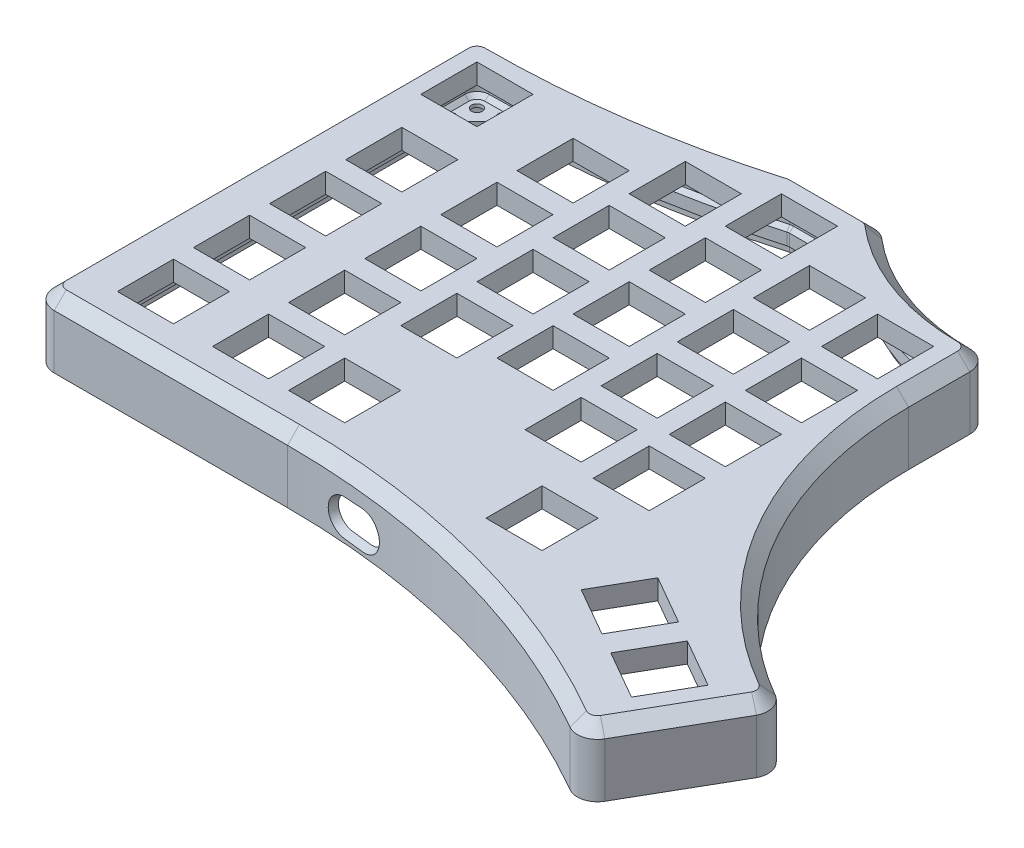
SolidWorks part; units mm, degrees
ref_plane "Front Plane" through (0, 0, 0) normal (0, 0, 1) x (1, 0, 0)
ref_plane "Top Plane" through (0, 0, 0) normal (0, 1, 0) x (1, 0, 0)
ref_plane "Right Plane" through (0, 0, 0) normal (1, 0, 0) x (0, 0, -1)
sketch "Main" plane through (0, 0, 0) normal (0, 1, 0) x (1, 0, 0)
  line L0 (6.4754, 3.5) -> (12.8, 6.5) construction
  line L1 (0, 0) -> (18, 0) construction
  line L2 (0, 0) -> (0, 18) construction
  line L3 (0, 18) -> (18, 18) construction
  line L4 (18, 0) -> (18, 18) construction
  line L5 (2, 16) -> (16, 16)
  line L6 (2, 16) -> (2, 2)
  line L7 (2, 2) -> (16, 2)
  line L8 (16, 16) -> (16, 2)
  line L18 (9, 9) -> (6.4754, 3.5) construction
  line L20 (9, 9) -> (12.8, 6.5) construction
  line L22 (25.4754, 12.5) -> (31.8, 15.5) construction
  line L23 (19, 9) -> (37, 9) construction
  line L24 (19, 9) -> (19, 27) construction
  line L25 (19, 27) -> (37, 27) construction
  line L26 (37, 9) -> (37, 27) construction
  line L27 (21, 25) -> (35, 25)
  line L28 (21, 25) -> (21, 11)
  line L29 (21, 11) -> (35, 11)
  line L30 (35, 25) -> (35, 11)
  line L31 (28, 18) -> (25.4754, 12.5) construction
  line L32 (28, 18) -> (31.8, 15.5) construction
  line L33 (44.4754, 17.5) -> (50.8, 20.5) construction
  line L34 (38, 14) -> (56, 14) construction
  line L35 (38, 14) -> (38, 32) construction
  line L36 (38, 32) -> (56, 32) construction
  line L37 (56, 14) -> (56, 32) construction
  line L38 (40, 30) -> (54, 30)
  line L39 (40, 30) -> (40, 16)
  line L40 (40, 16) -> (54, 16)
  line L41 (54, 30) -> (54, 16)
  line L42 (47, 23) -> (44.4754, 17.5) construction
  line L43 (47, 23) -> (50.8, 20.5) construction
  line L44 (63.4754, 5.5) -> (69.8, 8.5) construction
  line L45 (57, 2) -> (75, 2) construction
  line L46 (57, 2) -> (57, 20) construction
  line L47 (57, 20) -> (75, 20) construction
  line L48 (75, 2) -> (75, 20) construction
  line L49 (59, 18) -> (73, 18)
  line L50 (59, 18) -> (59, 4)
  line L51 (59, 4) -> (73, 4)
  line L52 (73, 18) -> (73, 4)
  line L53 (66, 11) -> (63.4754, 5.5) construction
  line L54 (66, 11) -> (69.8, 8.5) construction
  line L55 (82.4754, 3.5) -> (88.8, 6.5) construction
  line L56 (76, 0) -> (94, 0) construction
  line L57 (76, 0) -> (76, 18) construction
  line L58 (76, 18) -> (94, 18) construction
  line L59 (94, 0) -> (94, 18) construction
  line L60 (78, 16) -> (92, 16)
  line L61 (78, 16) -> (78, 2)
  line L62 (78, 2) -> (92, 2)
  line L63 (92, 16) -> (92, 2)
  line L64 (85, 9) -> (82.4754, 3.5) construction
  line L65 (85, 9) -> (88.8, 6.5) construction
  line L88 (2, -3) -> (16, -3)
  line L89 (2, -3) -> (2, -17)
  line L90 (2, -17) -> (16, -17)
  line L91 (16, -3) -> (16, -17)
  line L92 (21, 6) -> (35, 6)
  line L93 (21, 6) -> (21, -8)
  line L94 (21, -8) -> (35, -8)
  line L95 (35, 6) -> (35, -8)
  line L96 (40, 11) -> (54, 11)
  line L97 (40, 11) -> (40, -3)
  line L98 (40, -3) -> (54, -3)
  line L99 (54, 11) -> (54, -3)
  line L100 (59, -1) -> (73, -1)
  line L101 (59, -1) -> (59, -15)
  line L102 (59, -15) -> (73, -15)
  line L103 (73, -1) -> (73, -15)
  line L104 (78, -3) -> (92, -3)
  line L105 (78, -3) -> (78, -17)
  line L106 (78, -17) -> (92, -17)
  line L107 (92, -3) -> (92, -17)
  line L116 (6.4754, -15.5) -> (12.8, -12.5) construction
  line L117 (0, -19) -> (18, -19) construction
  line L118 (0, -19) -> (0, -1) construction
  line L119 (0, -1) -> (18, -1) construction
  line L120 (18, -19) -> (18, -1) construction
  line L121 (9, -10) -> (6.4754, -15.5) construction
  line L122 (9, -10) -> (12.8, -12.5) construction
  line L123 (25.4754, -6.5) -> (31.8, -3.5) construction
  line L124 (19, -10) -> (37, -10) construction
  line L125 (19, -10) -> (19, 8) construction
  line L126 (19, 8) -> (37, 8) construction
  line L127 (37, -10) -> (37, 8) construction
  line L128 (28, -1) -> (25.4754, -6.5) construction
  line L129 (28, -1) -> (31.8, -3.5) construction
  line L130 (44.4754, -1.5) -> (50.8, 1.5) construction
  line L131 (38, -5) -> (56, -5) construction
  line L132 (38, -5) -> (38, 13) construction
  line L133 (38, 13) -> (56, 13) construction
  line L134 (56, -5) -> (56, 13) construction
  line L135 (47, 4) -> (44.4754, -1.5) construction
  line L136 (47, 4) -> (50.8, 1.5) construction
  line L137 (63.4754, -13.5) -> (69.8, -10.5) construction
  line L138 (57, -17) -> (75, -17) construction
  line L139 (57, -17) -> (57, 1) construction
  line L140 (57, 1) -> (75, 1) construction
  line L141 (75, -17) -> (75, 1) construction
  line L142 (66, -8) -> (63.4754, -13.5) construction
  line L143 (66, -8) -> (69.8, -10.5) construction
  line L144 (82.4754, -15.5) -> (88.8, -12.5) construction
  line L145 (76, -19) -> (94, -19) construction
  line L146 (76, -19) -> (76, -1) construction
  line L147 (76, -1) -> (94, -1) construction
  line L148 (94, -19) -> (94, -1) construction
  line L149 (85, -10) -> (82.4754, -15.5) construction
  line L150 (85, -10) -> (88.8, -12.5) construction
  line L165 (2, -22) -> (16, -22)
  line L166 (2, -22) -> (2, -36)
  line L167 (2, -36) -> (16, -36)
  line L168 (16, -22) -> (16, -36)
  line L169 (21, -13) -> (35, -13)
  line L170 (21, -13) -> (21, -27)
  line L171 (21, -27) -> (35, -27)
  line L172 (35, -13) -> (35, -27)
  line L173 (40, -8) -> (54, -8)
  line L174 (40, -8) -> (40, -22)
  line L175 (40, -22) -> (54, -22)
  line L176 (54, -8) -> (54, -22)
  line L177 (59, -20) -> (73, -20)
  line L178 (59, -20) -> (59, -34)
  line L179 (59, -34) -> (73, -34)
  line L180 (73, -20) -> (73, -34)
  line L181 (78, -22) -> (92, -22)
  line L182 (78, -22) -> (78, -36)
  line L183 (78, -36) -> (92, -36)
  line L184 (92, -22) -> (92, -36)
  line L193 (6.4754, -34.5) -> (12.8, -31.5) construction
  line L194 (0, -38) -> (18, -38) construction
  line L195 (0, -38) -> (0, -20) construction
  line L196 (0, -20) -> (18, -20) construction
  line L197 (18, -38) -> (18, -20) construction
  line L198 (9, -29) -> (6.4754, -34.5) construction
  line L199 (9, -29) -> (12.8, -31.5) construction
  line L200 (25.4754, -25.5) -> (31.8, -22.5) construction
  line L201 (19, -29) -> (37, -29) construction
  line L202 (19, -29) -> (19, -11) construction
  line L203 (19, -11) -> (37, -11) construction
  line L204 (37, -29) -> (37, -11) construction
  line L205 (28, -20) -> (25.4754, -25.5) construction
  line L206 (28, -20) -> (31.8, -22.5) construction
  line L207 (44.4754, -20.5) -> (50.8, -17.5) construction
  line L208 (38, -24) -> (56, -24) construction
  line L209 (38, -24) -> (38, -6) construction
  line L210 (38, -6) -> (56, -6) construction
  line L211 (56, -24) -> (56, -6) construction
  line L212 (47, -15) -> (44.4754, -20.5) construction
  line L213 (47, -15) -> (50.8, -17.5) construction
  line L214 (63.4754, -32.5) -> (69.8, -29.5) construction
  line L215 (57, -36) -> (75, -36) construction
  line L216 (57, -36) -> (57, -18) construction
  line L217 (57, -18) -> (75, -18) construction
  line L218 (75, -36) -> (75, -18) construction
  line L219 (66, -27) -> (63.4754, -32.5) construction
  line L220 (66, -27) -> (69.8, -29.5) construction
  line L221 (82.4754, -34.5) -> (88.8, -31.5) construction
  line L222 (76, -38) -> (94, -38) construction
  line L223 (76, -38) -> (76, -20) construction
  line L224 (76, -20) -> (94, -20) construction
  line L225 (94, -38) -> (94, -20) construction
  line L226 (85, -29) -> (82.4754, -34.5) construction
  line L227 (85, -29) -> (88.8, -31.5) construction
  line L242 (2, -41) -> (16, -41)
  line L243 (2, -41) -> (2, -55)
  line L244 (2, -55) -> (16, -55)
  line L245 (16, -41) -> (16, -55)
  line L246 (21, -32) -> (35, -32)
  line L247 (21, -32) -> (21, -46)
  line L248 (21, -46) -> (35, -46)
  line L249 (35, -32) -> (35, -46)
  line L250 (40, -27) -> (54, -27)
  line L251 (40, -27) -> (40, -41)
  line L252 (40, -41) -> (54, -41)
  line L253 (54, -27) -> (54, -41)
  line L254 (59, -39) -> (73, -39)
  line L255 (59, -39) -> (59, -53)
  line L256 (59, -53) -> (73, -53)
  line L257 (73, -39) -> (73, -53)
  line L258 (78, -41) -> (92, -41)
  line L259 (78, -41) -> (78, -55)
  line L260 (78, -55) -> (92, -55)
  line L261 (92, -41) -> (92, -55)
  line L270 (6.4754, -53.5) -> (12.8, -50.5) construction
  line L271 (0, -57) -> (18, -57) construction
  line L272 (0, -57) -> (0, -39) construction
  line L273 (0, -39) -> (18, -39) construction
  line L274 (18, -57) -> (18, -39) construction
  line L275 (9, -48) -> (6.4754, -53.5) construction
  line L276 (9, -48) -> (12.8, -50.5) construction
  line L277 (25.4754, -44.5) -> (31.8, -41.5) construction
  line L278 (19, -48) -> (37, -48) construction
  line L279 (19, -48) -> (19, -30) construction
  line L280 (19, -30) -> (37, -30) construction
  line L281 (37, -48) -> (37, -30) construction
  line L282 (28, -39) -> (25.4754, -44.5) construction
  line L283 (28, -39) -> (31.8, -41.5) construction
  line L284 (44.4754, -39.5) -> (50.8, -36.5) construction
  line L285 (38, -43) -> (56, -43) construction
  line L286 (38, -43) -> (38, -25) construction
  line L287 (38, -25) -> (56, -25) construction
  line L288 (56, -43) -> (56, -25) construction
  line L289 (47, -34) -> (44.4754, -39.5) construction
  line L290 (47, -34) -> (50.8, -36.5) construction
  line L291 (63.4754, -51.5) -> (69.8, -48.5) construction
  line L292 (57, -55) -> (75, -55) construction
  line L293 (57, -55) -> (57, -37) construction
  line L294 (57, -37) -> (75, -37) construction
  line L295 (75, -55) -> (75, -37) construction
  line L296 (66, -46) -> (63.4754, -51.5) construction
  line L297 (66, -46) -> (69.8, -48.5) construction
  line L298 (82.4754, -53.5) -> (88.8, -50.5) construction
  line L299 (76, -57) -> (94, -57) construction
  line L300 (76, -57) -> (76, -39) construction
  line L301 (76, -39) -> (94, -39) construction
  line L302 (94, -57) -> (94, -39) construction
  line L303 (85, -48) -> (82.4754, -53.5) construction
  line L304 (85, -48) -> (88.8, -50.5) construction
  line L312 (6.4754, -72.5) -> (12.8, -69.5) construction
  line L313 (0, -76) -> (18, -76) construction
  line L314 (0, -76) -> (0, -58) construction
  line L315 (0, -58) -> (18, -58) construction
  line L316 (18, -76) -> (18, -58) construction
  line L317 (2, -60) -> (16, -60)
  line L318 (2, -60) -> (2, -74)
  line L323 (21, -60) -> (35, -60)
  line L324 (21, -60) -> (21, -74)
  line L325 (21, -74) -> (35, -74)
  line L326 (35, -60) -> (35, -74)
  line L327 (25.4754, -72.5) -> (31.8, -69.5) construction
  line L328 (19, -76) -> (37, -76) construction
  line L329 (19, -76) -> (19, -58) construction
  line L330 (-22.0246, 8) -> (-15.7, 11) construction
  line L331 (-28.5, 4.5) -> (-10.5, 4.5) construction
  line L332 (-28.5, 4.5) -> (-28.5, 22.5) construction
  line L333 (-28.5, 22.5) -> (-10.5, 22.5) construction
  line L334 (-10.5, 4.5) -> (-10.5, 22.5) construction
  line L335 (-26.5, 20.5) -> (-12.5, 20.5)
  line L336 (-26.5, 20.5) -> (-26.5, 6.5)
  line L337 (-26.5, 6.5) -> (-12.5, 6.5)
  line L338 (-12.5, 20.5) -> (-12.5, 6.5)
  line L339 (-19.5, 13.5) -> (-22.0246, 8) construction
  line L340 (-19.5, 13.5) -> (-15.7, 11) construction
  line L341 (-21.75, -41) -> (-7.75, -41)
  line L342 (-21.75, -41) -> (-21.75, -55)
  line L343 (-21.75, -55) -> (-7.75, -55)
  line L344 (-7.75, -41) -> (-7.75, -55)
  line L345 (-17.2746, -53.5) -> (-10.95, -50.5) construction
  line L346 (-28.5, -57) -> (-1, -57) construction
  line L347 (-28.5, -57) -> (-28.5, -39) construction
  line L348 (-28.5, -39) -> (-1, -39) construction
  line L349 (-1, -57) -> (-1, -39) construction
  line L350 (-14.75, -48) -> (-17.2746, -53.5) construction
  line L351 (-14.75, -48) -> (-10.95, -50.5) construction
  line L352 (-21.75, -22) -> (-7.75, -22)
  line L353 (-21.75, -22) -> (-21.75, -36)
  line L354 (2, -74) -> (16, -74)
  line L355 (16, -60) -> (16, -74)
  line L356 (9, -67) -> (6.4754, -72.5) construction
  line L357 (9, -67) -> (12.8, -69.5) construction
  line L358 (-17.2746, -72.5) -> (-10.95, -69.5) construction
  line L359 (-28.5, -76) -> (-1, -76) construction
  line L360 (-28.5, -76) -> (-28.5, -58) construction
  line L361 (-28.5, -58) -> (-1, -58) construction
  line L362 (-1, -76) -> (-1, -58) construction
  line L363 (-21.75, -60) -> (-7.75, -60)
  line L364 (-21.75, -60) -> (-21.75, -74)
  line L365 (-21.75, -74) -> (-7.75, -74)
  line L366 (-7.75, -60) -> (-7.75, -74)
  line L367 (-14.75, -67) -> (-17.2746, -72.5) construction
  line L368 (-14.75, -67) -> (-10.95, -69.5) construction
  line L369 (-21.75, -36) -> (-7.75, -36)
  line L370 (-7.75, -22) -> (-7.75, -36)
  line L371 (-17.2746, -34.5) -> (-10.95, -31.5) construction
  line L372 (-28.5, -38) -> (-1, -38) construction
  line L373 (-28.5, -38) -> (-28.5, -20) construction
  line L374 (-28.5, -20) -> (-1, -20) construction
  line L375 (-1, -38) -> (-1, -20) construction
  line L376 (-14.75, -29) -> (-17.2746, -34.5) construction
  line L377 (-14.75, -29) -> (-10.95, -31.5) construction
  line L378 (-21.75, -3) -> (-7.75, -3)
  line L379 (-21.75, -3) -> (-21.75, -17)
  line L380 (-21.75, -17) -> (-7.75, -17)
  line L381 (-7.75, -3) -> (-7.75, -17)
  line L382 (-17.2746, -15.5) -> (-10.95, -12.5) construction
  line L383 (-28.5, -19) -> (-1, -19) construction
  line L384 (-28.5, -19) -> (-28.5, -1) construction
  line L385 (-28.5, -1) -> (-1, -1) construction
  line L386 (-1, -19) -> (-1, -1) construction
  line L387 (-14.75, -10) -> (-17.2746, -15.5) construction
  line L388 (-14.75, -10) -> (-10.95, -12.5) construction
  line L393 (109.2068, -61.578) -> (124.8116, -70.5498) construction
  line L394 (109.2068, -61.578) -> (95.5, -85.4186) construction
  line L398 (124.8116, -70.5498) -> (111.1047, -94.3903) construction
  line L402 (77.7254, -75.5) -> (84.05, -72.5) construction
  line L403 (66.5, -79) -> (94, -79) construction
  line L404 (66.5, -79) -> (66.5, -61) construction
  line L405 (66.5, -61) -> (94, -61) construction
  line L406 (94, -79) -> (94, -61) construction
  line L407 (73.25, -63) -> (87.25, -63)
  line L408 (73.25, -63) -> (73.25, -77)
  line L409 (73.25, -77) -> (87.25, -77)
  line L410 (87.25, -63) -> (87.25, -77)
  line L411 (80.25, -70) -> (77.7254, -75.5) construction
  line L412 (80.25, -70) -> (84.05, -72.5) construction
  line L413 (95.5, -85.4186) -> (111.1047, -94.3903) construction
  line L414 (95.5, -85.4186) -> (124.8116, -70.5498) construction
  line L415 (80.25, -130) -> (110.1558, -77.9842) construction
  line L416 (107.5763, -68.4267) -> (119.7133, -75.4047)
  line L417 (107.5763, -68.4267) -> (100.5983, -80.5637)
  line L418 (119.7133, -75.4047) -> (112.7353, -87.5417)
  line L419 (100.5983, -80.5637) -> (112.7353, -87.5417)
  line L420 (107.5763, -68.4267) -> (112.7353, -87.5417) construction
  line L421 (105.2258, -81.494) -> (110.1558, -77.9842) construction
  line L422 (110.1558, -77.9842) -> (112.204, -82.0455) construction
  line L423 (112.204, -82.0455) -> (105.2258, -81.494) construction
  line L424 (126.5454, -71.5466) -> (142.1502, -80.5184) construction
  line L425 (126.5454, -71.5466) -> (112.8386, -95.3872) construction
  line L426 (142.1502, -80.5184) -> (128.4433, -104.3589) construction
  line L427 (112.8386, -95.3872) -> (128.4433, -104.3589) construction
  line L428 (112.8386, -95.3872) -> (142.1502, -80.5184) construction
  line L430 (124.9149, -78.3953) -> (137.0519, -85.3733)
  line L431 (124.9149, -78.3953) -> (117.9369, -90.5323)
  line L432 (137.0519, -85.3733) -> (130.0739, -97.5103)
  line L433 (117.9369, -90.5323) -> (130.0739, -97.5103)
  line L434 (124.9149, -78.3953) -> (130.0739, -97.5103) construction
  line L435 (122.5644, -91.4626) -> (127.4944, -87.9528) construction
  line L436 (127.4944, -87.9528) -> (129.5426, -92.0141) construction
  line L437 (129.5426, -92.0141) -> (122.5644, -91.4626) construction
  line L448 (19, -58) -> (37, -58) construction
  line L449 (37, -76) -> (37, -58) construction
  line L450 (28, -67) -> (25.4754, -72.5) construction
  line L451 (28, -67) -> (31.8, -69.5) construction
  circle A0 centre (9, 9) radius 2 construction
  circle A1 centre (6.4754, 3.5) radius 1.5 construction
  circle A2 centre (12.8, 6.5) radius 1.5 construction
  circle A6 centre (28, 18) radius 2 construction
  circle A7 centre (25.4754, 12.5) radius 1.5 construction
  circle A8 centre (31.8, 15.5) radius 1.5 construction
  circle A9 centre (47, 23) radius 2 construction
  circle A10 centre (44.4754, 17.5) radius 1.5 construction
  circle A11 centre (50.8, 20.5) radius 1.5 construction
  circle A12 centre (66, 11) radius 2 construction
  circle A13 centre (63.4754, 5.5) radius 1.5 construction
  circle A14 centre (69.8, 8.5) radius 1.5 construction
  circle A15 centre (85, 9) radius 2 construction
  circle A16 centre (82.4754, 3.5) radius 1.5 construction
  circle A17 centre (88.8, 6.5) radius 1.5 construction
  circle A24 centre (9, -10) radius 2 construction
  circle A25 centre (6.4754, -15.5) radius 1.5 construction
  circle A26 centre (12.8, -12.5) radius 1.5 construction
  circle A27 centre (28, -1) radius 2 construction
  circle A28 centre (25.4754, -6.5) radius 1.5 construction
  circle A29 centre (31.8, -3.5) radius 1.5 construction
  circle A30 centre (47, 4) radius 2 construction
  circle A31 centre (44.4754, -1.5) radius 1.5 construction
  circle A32 centre (50.8, 1.5) radius 1.5 construction
  circle A33 centre (66, -8) radius 2 construction
  circle A34 centre (63.4754, -13.5) radius 1.5 construction
  circle A35 centre (69.8, -10.5) radius 1.5 construction
  circle A36 centre (85, -10) radius 2 construction
  circle A37 centre (82.4754, -15.5) radius 1.5 construction
  circle A38 centre (88.8, -12.5) radius 1.5 construction
  circle A45 centre (9, -29) radius 2 construction
  circle A46 centre (6.4754, -34.5) radius 1.5 construction
  circle A47 centre (12.8, -31.5) radius 1.5 construction
  circle A48 centre (28, -20) radius 2 construction
  circle A49 centre (25.4754, -25.5) radius 1.5 construction
  circle A50 centre (31.8, -22.5) radius 1.5 construction
  circle A51 centre (47, -15) radius 2 construction
  circle A52 centre (44.4754, -20.5) radius 1.5 construction
  circle A53 centre (50.8, -17.5) radius 1.5 construction
  circle A54 centre (66, -27) radius 2 construction
  circle A55 centre (63.4754, -32.5) radius 1.5 construction
  circle A56 centre (69.8, -29.5) radius 1.5 construction
  circle A57 centre (85, -29) radius 2 construction
  circle A58 centre (82.4754, -34.5) radius 1.5 construction
  circle A59 centre (88.8, -31.5) radius 1.5 construction
  circle A63 centre (9, -67) radius 2 construction
  circle A64 centre (6.4754, -72.5) radius 1.5 construction
  circle A65 centre (12.8, -69.5) radius 1.5 construction
  circle A66 centre (9, -48) radius 2 construction
  circle A67 centre (6.4754, -53.5) radius 1.5 construction
  circle A68 centre (12.8, -50.5) radius 1.5 construction
  circle A69 centre (28, -39) radius 2 construction
  circle A70 centre (25.4754, -44.5) radius 1.5 construction
  circle A71 centre (31.8, -41.5) radius 1.5 construction
  circle A72 centre (47, -34) radius 2 construction
  circle A73 centre (44.4754, -39.5) radius 1.5 construction
  circle A74 centre (50.8, -36.5) radius 1.5 construction
  circle A75 centre (66, -46) radius 2 construction
  circle A76 centre (63.4754, -51.5) radius 1.5 construction
  circle A77 centre (69.8, -48.5) radius 1.5 construction
  circle A78 centre (85, -48) radius 2 construction
  circle A79 centre (82.4754, -53.5) radius 1.5 construction
  circle A80 centre (88.8, -50.5) radius 1.5 construction
  circle A81 centre (-14.75, -67) radius 2 construction
  circle A82 centre (-17.2746, -72.5) radius 1.5 construction
  circle A83 centre (-10.95, -69.5) radius 1.5 construction
  circle A84 centre (28, -67) radius 2 construction
  circle A85 centre (25.4754, -72.5) radius 1.5 construction
  circle A86 centre (31.8, -69.5) radius 1.5 construction
  circle A87 centre (-19.5, 13.5) radius 2 construction
  circle A88 centre (-22.0246, 8) radius 1.5 construction
  circle A89 centre (-15.7, 11) radius 1.5 construction
  circle A90 centre (-14.75, -48) radius 2 construction
  circle A91 centre (-17.2746, -53.5) radius 1.5 construction
  circle A92 centre (-10.95, -50.5) radius 1.5 construction
  circle A93 centre (-14.75, -29) radius 2 construction
  circle A94 centre (-17.2746, -34.5) radius 1.5 construction
  circle A95 centre (-10.95, -31.5) radius 1.5 construction
  circle A96 centre (-14.75, -10) radius 2 construction
  circle A97 centre (-17.2746, -15.5) radius 1.5 construction
  circle A98 centre (-10.95, -12.5) radius 1.5 construction
  circle A102 centre (80.25, -70) radius 2 construction
  circle A103 centre (77.7254, -75.5) radius 1.5 construction
  circle A104 centre (84.05, -72.5) radius 1.5 construction
  circle A105 centre (80.25, -130) radius 60 construction
  circle A106 centre (110.1558, -77.9842) radius 2 construction
  circle A107 centre (105.2258, -81.494) radius 1.5 construction
  circle A108 centre (112.204, -82.0455) radius 1.5 construction
  circle A109 centre (127.4944, -87.9528) radius 2 construction
  circle A110 centre (122.5644, -91.4626) radius 1.5 construction
  circle A111 centre (129.5426, -92.0141) radius 1.5 construction
  circle A112 centre (62, -66) radius 1.5 construction
  point P9 (9, 16)
  point P10 (9, 18)
  point P11 (2, 9)
  point P12 (0, 9)
  point P30 (28, 25)
  point P31 (28, 27)
  point P32 (21, 18)
  point P33 (19, 18)
  point P46 (47, 30)
  point P47 (47, 32)
  point P48 (40, 23)
  point P49 (38, 23)
  point P64 (66, 18)
  point P65 (66, 20)
  point P66 (59, 11)
  point P67 (57, 11)
  point P82 (85, 16)
  point P83 (85, 18)
  point P84 (78, 9)
  point P85 (76, 9)
  point P102 (9, -60)
  point P103 (9, -58)
  point P104 (2, -67)
  point P105 (0, -67)
  point P124 (-14.75, -60)
  point P125 (-14.75, -58)
  point P126 (-21.75, -67)
  point P127 (-28.5, -67)
  point P297 (-19.5, 20.5)
  point P298 (-19.5, 22.5)
  point P299 (-26.5, 13.5)
  point P300 (-28.5, 13.5)
  point P423 (103.3024, -89.9045)
  point P444 (80.25, -63)
  point P445 (80.25, -61)
  point P446 (73.25, -70)
  point P447 (66.5, -70)
  dimension "D6" = 4
  dimension "D7" = 3
  dimension "D10" = 1
  dimension "D11" = 12
  dimension "D21" = 9.5
  dimension "D22" = 1.5
  dimension "D26" = 120
  dimension "D28" = 3
  dimension "D1" = 18
  dimension "D2" = 14
  dimension "D3" = 3.2
  dimension "D4" = 4.5
  dimension "D5" = 7
  dimension "D8" = 1
  dimension "D9" = 5
  dimension "D12" = 1
  dimension "D13" = 9
  dimension "D14" = 1
  dimension "D15" = 2
  dimension "D16" = 2
  dimension "D17" = 27.5
  dimension "D18" = 1
  dimension "D20" = 1
  dimension "D24" = 1
  dimension "D25" = 8
  dimension "D27" = 2
  dimension "D29" = 15
  dimension "D30" = 32
  dimension "D19" = 4
  dimension "D23" = 4
sketch "Sketch1" plane through (0, 0, 0) normal (0, 1, 0) x (1, 0, 0)
  line L0 (-33.5, 22.5) -> (-33.5, -78)
  line L1 (-28.5, -83) -> (29.7127, -83)
  line L2 (132.778, -106.8511) -> (146.594, -82.8206)
  line L3 (99, 2.7142) -> (99, 18)
  line L6 (38, 32) -> (56, 32) construction
  line L7 (-28.5, -76) -> (-28.5, -58) construction
  line L8 (144.6447, -76.1796) -> (94, -47.0621) construction
  line L9 (142.1502, -80.5184) -> (128.4433, -104.3589) construction
  line L10 (94, 0) -> (94, 18) construction
  line L11 (94, -57) -> (94, -39) construction
  line L12 (128.4433, -104.3589) -> (125.9512, -108.6936) construction
  line L13 (109.2068, -61.578) -> (124.8116, -70.5498) construction
  line L14 (125.9512, -108.6936) -> (74.3045, -79) construction
  line L15 (66.5, -79) -> (94, -79) construction
  line L17 (95.5, -85.4186) -> (111.1047, -94.3903) construction
  line L20 (94, 23) -> (56, 23) construction
  line L21 (56, 14) -> (56, 32) construction
  line L23 (38, 37) -> (56, 37)
  line L27 (38, 14) -> (38, 32) construction
  line L28 (-28.5, 4.5) -> (-28.5, 22.5) construction
  line L29 (-31.5, 22.5) -> (-31.5, -78) construction
  line L30 (-28.5, -81) -> (29.7127, -81) construction
  line L31 (131.0441, -105.8542) -> (144.8356, -81.8665) construction
  line L32 (97, 2.7142) -> (97, 18) construction
  line L33 (38, 35) -> (56, 35) construction
  line L39 (107.5763, -68.4267) -> (119.7133, -75.4047)
  line L40 (-26.5, 20.5) -> (-12.5, 20.5)
  line L41 (-26.5, 20.5) -> (-26.5, 6.5)
  line L42 (-26.5, 6.5) -> (-12.5, 6.5)
  line L43 (-12.5, 20.5) -> (-12.5, 6.5)
  line L44 (-21.75, -3) -> (-7.75, -3)
  line L45 (-21.75, -3) -> (-21.75, -17)
  line L46 (-21.75, -17) -> (-7.75, -17)
  line L47 (-7.75, -3) -> (-7.75, -17)
  line L48 (-21.75, -22) -> (-7.75, -22)
  line L49 (-21.75, -22) -> (-21.75, -36)
  line L50 (-21.75, -36) -> (-7.75, -36)
  line L51 (-7.75, -22) -> (-7.75, -36)
  line L52 (-21.75, -41) -> (-7.75, -41)
  line L53 (-21.75, -41) -> (-21.75, -55)
  line L54 (-21.75, -55) -> (-7.75, -55)
  line L55 (-7.75, -41) -> (-7.75, -55)
  line L56 (-21.75, -60) -> (-7.75, -60)
  line L57 (-21.75, -60) -> (-21.75, -74)
  line L58 (-21.75, -74) -> (-7.75, -74)
  line L59 (-7.75, -60) -> (-7.75, -74)
  line L60 (2, 16) -> (16, 16)
  line L61 (2, 16) -> (2, 2)
  line L62 (2, 2) -> (16, 2)
  line L63 (16, 16) -> (16, 2)
  line L64 (2, -3) -> (16, -3)
  line L65 (2, -3) -> (2, -17)
  line L66 (2, -17) -> (16, -17)
  line L67 (16, -3) -> (16, -17)
  line L68 (2, -22) -> (16, -22)
  line L69 (2, -22) -> (2, -36)
  line L70 (2, -36) -> (16, -36)
  line L71 (16, -22) -> (16, -36)
  line L72 (2, -41) -> (16, -41)
  line L73 (2, -41) -> (2, -55)
  line L74 (2, -55) -> (16, -55)
  line L75 (16, -41) -> (16, -55)
  line L76 (2, -60) -> (16, -60)
  line L77 (2, -60) -> (2, -74)
  line L78 (2, -74) -> (16, -74)
  line L79 (16, -60) -> (16, -74)
  line L80 (21, -60) -> (35, -60)
  line L81 (21, -60) -> (21, -74)
  line L82 (21, -74) -> (35, -74)
  line L83 (35, -60) -> (35, -74)
  line L84 (21, -32) -> (35, -32)
  line L85 (21, -32) -> (21, -46)
  line L86 (21, -46) -> (35, -46)
  line L87 (35, -32) -> (35, -46)
  line L88 (21, 25) -> (35, 25)
  line L89 (21, 25) -> (21, 11)
  line L90 (21, 11) -> (35, 11)
  line L91 (35, 25) -> (35, 11)
  line L92 (21, 6) -> (35, 6)
  line L93 (21, 6) -> (21, -8)
  line L94 (21, -8) -> (35, -8)
  line L95 (35, 6) -> (35, -8)
  line L96 (21, -13) -> (35, -13)
  line L97 (21, -13) -> (21, -27)
  line L98 (21, -27) -> (35, -27)
  line L99 (35, -13) -> (35, -27)
  line L100 (40, 30) -> (54, 30)
  line L101 (40, 30) -> (40, 16)
  line L102 (40, 16) -> (54, 16)
  line L103 (54, 30) -> (54, 16)
  line L104 (40, 11) -> (54, 11)
  line L105 (40, 11) -> (40, -3)
  line L106 (40, -3) -> (54, -3)
  line L107 (54, 11) -> (54, -3)
  line L108 (40, -8) -> (54, -8)
  line L109 (40, -8) -> (40, -22)
  line L110 (40, -22) -> (54, -22)
  line L111 (54, -8) -> (54, -22)
  line L112 (40, -27) -> (54, -27)
  line L113 (40, -27) -> (40, -41)
  line L114 (40, -41) -> (54, -41)
  line L115 (54, -27) -> (54, -41)
  line L116 (59, 18) -> (73, 18)
  line L117 (59, 18) -> (59, 4)
  line L118 (59, 4) -> (73, 4)
  line L119 (73, 18) -> (73, 4)
  line L120 (78, 16) -> (92, 16)
  line L121 (78, 16) -> (78, 2)
  line L122 (78, 2) -> (92, 2)
  line L123 (92, 16) -> (92, 2)
  line L124 (59, -1) -> (73, -1)
  line L125 (59, -1) -> (59, -15)
  line L126 (59, -15) -> (73, -15)
  line L127 (73, -1) -> (73, -15)
  line L128 (78, -3) -> (92, -3)
  line L129 (78, -3) -> (78, -17)
  line L130 (78, -17) -> (92, -17)
  line L131 (92, -3) -> (92, -17)
  line L132 (59, -20) -> (73, -20)
  line L133 (59, -20) -> (59, -34)
  line L134 (59, -34) -> (73, -34)
  line L135 (73, -20) -> (73, -34)
  line L136 (78, -22) -> (92, -22)
  line L137 (78, -22) -> (78, -36)
  line L138 (78, -36) -> (92, -36)
  line L139 (92, -22) -> (92, -36)
  line L140 (59, -39) -> (73, -39)
  line L141 (59, -39) -> (59, -53)
  line L142 (59, -53) -> (73, -53)
  line L143 (73, -39) -> (73, -53)
  line L144 (78, -41) -> (92, -41)
  line L145 (78, -41) -> (78, -55)
  line L146 (78, -55) -> (92, -55)
  line L147 (92, -41) -> (92, -55)
  line L148 (73.25, -63) -> (87.25, -63)
  line L149 (73.25, -63) -> (73.25, -77)
  line L150 (73.25, -77) -> (87.25, -77)
  line L151 (87.25, -63) -> (87.25, -77)
  line L152 (107.5763, -68.4267) -> (100.5983, -80.5637)
  line L153 (119.7133, -75.4047) -> (112.7353, -87.5417)
  line L154 (100.5983, -80.5637) -> (112.7353, -87.5417)
  line L155 (124.9149, -78.3953) -> (137.0519, -85.3733)
  line L156 (124.9149, -78.3953) -> (117.9369, -90.5323)
  line L157 (137.0519, -85.3733) -> (130.0739, -97.5103)
  line L158 (117.9369, -90.5323) -> (130.0739, -97.5103)
  arc A0 (29.7127, -83) -> (125.9512, -108.6936) centre (29.7127, -276.0835) cw
  arc A4 (94, 23) -> (59.2439, 35.8049) centre (94, 76.5714) cw
  arc A7 (36.6, 36.8) -> (-28.5, 27.5) centre (-28.5, 260) cw
  arc A10 (125.9512, -108.6936) -> (132.778, -106.8511) centre (128.4433, -104.3589) ccw
  arc A11 (-33.5, -78) -> (-28.5, -83) centre (-28.5, -78) ccw
  arc A14 (146.594, -82.8206) -> (144.6447, -76.1796) centre (142.1502, -80.5184) ccw
  arc A15 (144.6447, -76.1796) -> (99, 2.7142) centre (190.0036, 2.7142) cw
  arc A16 (99, 18) -> (94, 23) centre (94, 18) ccw
  arc A17 (-33.5, 22.5) -> (-28.5, 27.5) centre (-28.5, 22.5) cw
  arc A29 (36.6, 36.8) -> (38, 37) centre (38, 32) cw
  arc A30 (56, 37) -> (59.2439, 35.8049) centre (56, 32) cw
  arc A31 (37.16, 34.88) -> (-28.5, 25.5) centre (-28.5, 260) cw construction
  arc A32 (-31.5, 22.5) -> (-28.5, 25.5) centre (-28.5, 22.5) cw construction
  arc A33 (-31.5, -78) -> (-28.5, -81) centre (-28.5, -78) ccw construction
  arc A34 (29.7127, -81) -> (126.9481, -106.9597) centre (29.7127, -276.0835) cw construction
  arc A35 (126.9481, -106.9597) -> (131.0441, -105.8542) centre (128.4433, -104.3589) ccw construction
  arc A36 (144.8356, -81.8665) -> (143.6478, -77.9134) centre (142.1502, -80.5184) ccw construction
  arc A37 (143.6478, -77.9134) -> (97, 2.7142) centre (190.0036, 2.7142) cw construction
  arc A38 (97, 18) -> (94, 21) centre (94, 18) ccw construction
  arc A39 (94, 21) -> (57.9463, 34.2829) centre (94, 76.5714) cw construction
  arc A40 (56, 35) -> (57.9463, 34.2829) centre (56, 32) cw construction
  arc A41 (37.16, 34.88) -> (38, 35) centre (38, 32) cw construction
  dimension "D1" = 4
  dimension "D2" = 5
  dimension "D7" = 5.0048
  dimension "D8" = 5
  dimension "D3" = 5
  dimension "D4" = 5
  dimension "D5" = 5
  dimension "D6" = 5
  dimension "D9" = 2
extrude "Main_plate" add sketch "Sketch1" against normal blind 5
chamfer "Main_plate_chamfer" distance 3 16 edges at (146.9524, 0, 79.1088) (111.2334, 0, 42.859) (99, 0, -10.3571) (97.5355, 0, -21.5355) (75.4801, 0, -26.303) (4.3805, 0, -29.8367) (-32.0355, 0, -26.0355) (139.686, 0, 94.8358) (-33.5, 0, 27.75) (129.7462, 0, 109.1862) (-32.0355, 0, 81.5355) (79.5173, 0, 89.534) (0.6063, 0, 83) (57.7285, 0, -36.6917) (47, 0, -37) (37.2929, 0, -36.9497)
sketch "Sketch3" plane through (0, -5, 0) normal (0, -1, 0) x (1, 0, 0)
  line L0 (-28.5, 83) -> (29.7127, 83)
  line L1 (132.778, 106.8511) -> (146.594, 82.8206)
  line L2 (-33.5, 78) -> (-33.5, -22.5)
  line L3 (99, -18) -> (99, -2.7142)
  line L8 (38, -37) -> (56, -37)
  line L9 (-28.5, 81) -> (29.7127, 81)
  line L10 (131.0441, 105.8542) -> (144.8356, 81.8665)
  line L11 (97, -18) -> (97, -2.7142)
  line L12 (38, -35) -> (56, -35)
  line L13 (-31.5, 78) -> (-31.5, -22.5)
  arc A0 (29.7127, 83) -> (125.9512, 108.6936) centre (29.7127, 276.0835) ccw
  arc A1 (125.9512, 108.6936) -> (132.778, 106.8511) centre (128.4433, 104.3589) cw
  arc A2 (-28.5, 83) -> (-33.5, 78) centre (-28.5, 78) ccw
  arc A3 (-33.5, -22.5) -> (-28.5, -27.5) centre (-28.5, -22.5) ccw
  arc A8 (94, -23) -> (99, -18) centre (94, -18) ccw
  arc A10 (144.6447, 76.1796) -> (146.594, 82.8206) centre (142.1502, 80.5184) ccw
  arc A11 (144.6447, 76.1796) -> (99, -2.7142) centre (190.0036, -2.7142) ccw
  arc A23 (94, -23) -> (99, -18) centre (94, -18) ccw construction
  arc A24 (-28.5, -27.5) -> (36.6, -36.8) centre (-28.5, -260) cw
  arc A25 (36.6, -36.8) -> (38, -37) centre (38, -32) ccw
  arc A26 (94, -23) -> (59.2439, -35.8049) centre (94, -76.5714) ccw
  arc A27 (59.2439, -35.8049) -> (56, -37) centre (56, -32) cw
  arc A28 (29.7127, 81) -> (126.9481, 106.9597) centre (29.7127, 276.0835) ccw
  arc A29 (126.9481, 106.9597) -> (131.0441, 105.8542) centre (128.4433, 104.3589) cw
  arc A30 (143.6478, 77.9134) -> (144.8356, 81.8665) centre (142.1502, 80.5184) ccw
  arc A31 (143.6478, 77.9134) -> (97, -2.7142) centre (190.0036, -2.7142) ccw
  arc A32 (94, -21) -> (97, -18) centre (94, -18) ccw
  arc A33 (94, -21) -> (57.9463, -34.2829) centre (94, -76.5714) ccw
  arc A34 (57.9463, -34.2829) -> (56, -35) centre (56, -32) cw
  arc A35 (37.16, -34.88) -> (38, -35) centre (38, -32) ccw
  arc A36 (-28.5, -25.5) -> (37.16, -34.88) centre (-28.5, -260) cw
  arc A37 (-31.5, -22.5) -> (-28.5, -25.5) centre (-28.5, -22.5) ccw
  arc A38 (-28.5, 81) -> (-31.5, 78) centre (-28.5, 78) ccw
  dimension "D1" = 2
extrude "Wall" add sketch "Sketch3" along normal blind 11.5
sketch "Sketch4" plane through (0, -5, 0) normal (0, -1, 0) x (1, 0, 0)
  line L0 (54.62, 75.25) -> (54.62, 44.77) construction
  line L2 (56.12, 75.25) -> (56.12, 44.77)
  line L12 (53.12, 75.25) -> (53.12, 44.77)
  line L16 (39.38, 44.77) -> (39.38, 75.25) construction
  line L17 (37.88, 44.77) -> (37.88, 75.25)
  line L18 (40.88, 44.77) -> (40.88, 75.25)
  arc A9 (56.12, 75.25) -> (53.12, 75.25) centre (54.62, 75.25) ccw
  arc A10 (53.12, 44.77) -> (56.12, 44.77) centre (54.62, 44.77) ccw
  arc A11 (37.88, 44.77) -> (40.88, 44.77) centre (39.38, 44.77) ccw
  arc A12 (40.88, 75.25) -> (37.88, 75.25) centre (39.38, 75.25) ccw
  point P2 (54.62, 60.01)
  point P7 (39.38, 60.01)
  dimension "D1" = 3
extrude "Nice-nano_extrude" cut sketch "Sketch4" against normal blind 2
ref_plane "Plane1" through (0, -14.5, 0) normal (0, -1, 0) x (-1, 0, 0)
sketch "Sketch8" plane through (0, -14.5, 0) normal (0, -1, 0) x (-1, 0, 0)
  line L0 (-39.38, -80.2385) -> (-39.38, -81.2397)
  line L2 (-54.62, -81.5883) -> (-54.62, -82.5966)
  line L51 (-29.7127, -80) -> (28.5, -80)
  line L52 (30.5, -78) -> (30.5, 22.5)
  line L53 (-38, 34) -> (-56, 34)
  line L54 (-96, 18) -> (-96, 2.7142)
  line L55 (-143.9531, -81.395) -> (-130.1772, -105.3558)
  line L56 (-144.8356, -81.8665) -> (-131.0441, -105.8542)
  line L57 (-97, 18) -> (-97, 2.7142)
  line L58 (-38, 35) -> (-56, 35)
  line L59 (31.5, -78) -> (31.5, 22.5)
  line L60 (-29.7127, -81) -> (28.5, -81)
  line L61 (-144.8356, -81.8665) -> (-131.0441, -105.8542)
  line L62 (-97, 18) -> (-97, 2.7142)
  line L63 (-38, 35) -> (-56, 35)
  line L64 (31.5, -78) -> (31.5, 22.5)
  line L65 (-29.7127, -81) -> (28.5, -81)
  arc A0 (-54.62, -81.5883) -> (-127.4465, -106.0928) centre (-29.7127, -276.0835) ccw
  arc A1 (-29.7127, -80) -> (-127.4465, -106.0928) centre (-29.7127, -276.0835) ccw construction
  arc A2 (-54.62, -82.5966) -> (-126.9481, -106.9597) centre (-29.7127, -276.0835) ccw
  arc A3 (-29.7127, -81) -> (-126.9481, -106.9597) centre (-29.7127, -276.0835) ccw construction
  arc A4 (-40.88, -75.25) -> (-37.88, -75.25) centre (-39.38, -75.25) ccw construction
  arc A5 (-56.12, -75.25) -> (-53.12, -75.25) centre (-54.62, -75.25) ccw construction
  arc A91 (28.5, -80) -> (30.5, -78) centre (28.5, -78) ccw
  arc A92 (30.5, 22.5) -> (28.5, 24.5) centre (28.5, 22.5) ccw
  arc A93 (-37.44, 33.92) -> (28.5, 24.5) centre (28.5, 260) ccw
  arc A94 (-37.44, 33.92) -> (-38, 34) centre (-38, 32) ccw
  arc A95 (-56, 34) -> (-57.2976, 33.522) centre (-56, 32) ccw
  arc A96 (-94, 20) -> (-57.2976, 33.522) centre (-94, 76.5714) ccw
  arc A97 (-94, 20) -> (-96, 18) centre (-94, 18) ccw
  arc A98 (-143.1494, -78.7803) -> (-96, 2.7142) centre (-190.0036, 2.7142) ccw
  arc A99 (-143.1494, -78.7803) -> (-143.9531, -81.395) centre (-142.1502, -80.5184) ccw
  arc A100 (-130.1772, -105.3558) -> (-127.4465, -106.0928) centre (-128.4433, -104.3589) ccw
  arc A101 (-29.7127, -80) -> (-39.38, -80.2385) centre (-29.7127, -276.0835) ccw
  arc A102 (-29.7127, -81) -> (-126.9481, -106.9597) centre (-29.7127, -276.0835) ccw
  arc A103 (-131.0441, -105.8542) -> (-126.9481, -106.9597) centre (-128.4433, -104.3589) ccw
  arc A104 (-143.6478, -77.9134) -> (-144.8356, -81.8665) centre (-142.1502, -80.5184) ccw
  arc A105 (-143.6478, -77.9134) -> (-97, 2.7142) centre (-190.0036, 2.7142) ccw
  arc A106 (-94, 21) -> (-97, 18) centre (-94, 18) ccw
  arc A107 (-94, 21) -> (-57.9463, 34.2829) centre (-94, 76.5714) ccw
  arc A108 (-56, 35) -> (-57.9463, 34.2829) centre (-56, 32) ccw
  arc A109 (-37.16, 34.88) -> (-38, 35) centre (-38, 32) ccw
  arc A110 (-37.16, 34.88) -> (28.5, 25.5) centre (28.5, 260) ccw
  arc A111 (31.5, 22.5) -> (28.5, 25.5) centre (28.5, 22.5) ccw
  arc A112 (28.5, -81) -> (31.5, -78) centre (28.5, -78) ccw
  arc A113 (-29.7127, -81) -> (-39.38, -81.2397) centre (-29.7127, -276.0835) ccw
  arc A114 (-131.0441, -105.8542) -> (-126.9481, -106.9597) centre (-128.4433, -104.3589) ccw
  arc A115 (-143.6478, -77.9134) -> (-144.8356, -81.8665) centre (-142.1502, -80.5184) ccw
  arc A116 (-143.6478, -77.9134) -> (-97, 2.7142) centre (-190.0036, 2.7142) ccw
  arc A117 (-94, 21) -> (-97, 18) centre (-94, 18) ccw
  arc A118 (-94, 21) -> (-57.9463, 34.2829) centre (-94, 76.5714) ccw
  arc A119 (-56, 35) -> (-57.9463, 34.2829) centre (-56, 32) ccw
  arc A120 (-37.16, 34.88) -> (-38, 35) centre (-38, 32) ccw
  arc A121 (-37.16, 34.88) -> (28.5, 25.5) centre (28.5, 260) ccw
  arc A122 (31.5, 22.5) -> (28.5, 25.5) centre (28.5, 22.5) ccw
  arc A123 (28.5, -81) -> (31.5, -78) centre (28.5, -78) ccw
  point P29 (-54.62, -76.75)
  point P35 (-39.38, -76.75)
  dimension "D1" = 0
  dimension "D2" = 1
extrude "Side" add sketch "Sketch8" against normal blind 3
chamfer "Side_chamfer" distance 1 angle 45 17 edges at (137.9398, -11.5, 93.8604) (129.2251, -11.5, 107.2553) (34.5478, -11.5, 81.0599) (0.6063, -11.5, 81) (-30.6213, -11.5, 80.1213) (-31.5, -11.5, 27.75) (-30.6213, -11.5, -24.6213) (145.0279, -11.5, 79.6537) (37.5757, -11.5, -34.9698) (109.5023, -11.5, 43.8606) (47, -11.5, -35) (97, -11.5, -10.3571) (57.0371, -11.5, -34.815) (96.1213, -11.5, -20.1213) (74.7887, -11.5, -24.4264) (91.9871, -11.5, 91.2066) (4.6633, -11.5, -27.8568)
sketch "Sketch18" plane through (0, -14.5, 0) normal (0, -1, 0) x (1, 0, 0)
  line L15 (29.7127, 81) -> (-28.5, 81) construction
  line L16 (-31.5, 78) -> (-31.5, -22.5) construction
  line L17 (-26.5, -20.5) -> (-26.5, -6.5) construction
  line L18 (-23.427, 76.2747) -> (-24.6932, 81)
  line L21 (144.8356, 81.8665) -> (131.0441, 105.8542) construction
  line L22 (97, -18) -> (97, -2.7142) construction
  line L23 (-31.5, 78) -> (-31.5, -22.5) construction
  line L27 (-23.427, 76.2747) -> (-24.6524, 80.8476) construction
  line L28 (-25.8771, 79.6229) -> (-28.777, 80.3999) construction
  line L29 (-28.777, 80.3999) -> (-30.8999, 78.277) construction
  line L30 (-30.8999, 78.277) -> (-30.1229, 75.3771) construction
  line L31 (-30.1229, 75.3771) -> (-27.223, 74.6001) construction
  line L32 (-27.223, 74.6001) -> (-25.1001, 76.723) construction
  line L33 (-25.1001, 76.723) -> (-25.8771, 79.6229) construction
  line L34 (-24.6524, 80.8476) -> (-29.2253, 82.073) construction
  line L35 (-29.2253, 82.073) -> (-32.573, 78.7253) construction
  line L36 (-32.573, 78.7253) -> (-31.3476, 74.1524) construction
  line L37 (-31.3476, 74.1524) -> (-26.7747, 72.927) construction
  line L38 (-26.7747, 72.927) -> (-23.427, 76.2747)
  line L39 (-26.7747, 72.927) -> (-31.5, 74.1932)
  line L41 (-31.5, 74.1932) -> (-31.5, 81)
  line L42 (-31.5, 81) -> (-24.6932, 81)
  line L43 (-25.8771, -24.1234) -> (-25.1001, -21.2235) construction
  line L44 (-25.1001, -21.2235) -> (-27.223, -19.1006) construction
  line L45 (-27.223, -19.1006) -> (-30.1229, -19.8776) construction
  line L46 (-30.1229, -19.8776) -> (-30.8999, -22.7776) construction
  line L47 (-30.8999, -22.7776) -> (-28.777, -24.9004) construction
  line L48 (-28.777, -24.9004) -> (-25.8771, -24.1234) construction
  line L49 (-21.75, 60) -> (-21.75, 74) construction
  line L50 (-23.427, -20.7752) -> (-26.7747, -17.4276)
  line L51 (-26.7747, -17.4276) -> (-31.3476, -18.6529) construction
  line L52 (-31.3476, -18.6529) -> (-32.573, -23.2258) construction
  line L53 (-32.573, -23.2258) -> (-29.2253, -26.5735) construction
  line L54 (-29.2253, -26.5735) -> (-24.6524, -25.3482) construction
  line L55 (-24.6524, -25.3482) -> (-23.427, -20.7752) construction
  line L56 (-23.427, -20.7752) -> (-24.7013, -25.5308)
  line L57 (-26.7747, -17.4276) -> (-31.5, -18.6937)
  line L58 (-31.5, -18.6937) -> (-31.5, -25.4687)
  line L59 (-31.5, -25.4687) -> (-24.7013, -25.5308)
  line L60 (92, -2) -> (92, -16) construction
  line L61 (96.8476, -14.1545) -> (92.2747, -12.9292) construction
  line L62 (92.2747, -12.9292) -> (88.927, -16.2768)
  line L63 (88.927, -16.2768) -> (90.1524, -20.8498) construction
  line L64 (90.1524, -20.8498) -> (94.7253, -22.0751) construction
  line L65 (94.7253, -22.0751) -> (98.073, -18.7274) construction
  line L66 (98.073, -18.7274) -> (96.8476, -14.1545) construction
  line L67 (95.6229, -15.3792) -> (92.723, -14.6022) construction
  line L68 (92.723, -14.6022) -> (90.6001, -16.7251) construction
  line L69 (90.6001, -16.7251) -> (91.3771, -19.625) construction
  line L70 (91.3771, -19.625) -> (94.277, -20.402) construction
  line L71 (94.277, -20.402) -> (96.3999, -18.2791) construction
  line L72 (96.3999, -18.2791) -> (95.6229, -15.3792) construction
  line L73 (88.927, -16.2768) -> (90.227, -21.1282)
  line L74 (92.2747, -12.9292) -> (97, -14.1953)
  line L75 (97, -18) -> (97, -2.7142) construction
  line L76 (97, -14.1953) -> (97, -20.8724)
  line L77 (97, -20.8724) -> (90.227, -21.1282)
  line L78 (137.0519, 85.3733) -> (124.9149, 78.3953) construction
  line L79 (138.5692, 79.9256) -> (140.6882, 77.7988) construction
  line L80 (140.6882, 77.7988) -> (143.5896, 78.5706) construction
  line L81 (143.5896, 78.5706) -> (144.3718, 81.4691) construction
  line L82 (144.3718, 81.4691) -> (142.2528, 83.5958) construction
  line L83 (142.2528, 83.5958) -> (139.3515, 82.8241) construction
  line L84 (139.3515, 82.8241) -> (138.5692, 79.9256) construction
  line L85 (136.8953, 79.4803) -> (140.2369, 76.1266) construction
  line L86 (140.2369, 76.1266) -> (144.8121, 77.3436) construction
  line L87 (144.8121, 77.3436) -> (146.0457, 81.9144) construction
  line L88 (146.0457, 81.9144) -> (142.7041, 85.2681) construction
  line L89 (142.7041, 85.2681) -> (138.129, 84.051) construction
  line L90 (138.129, 84.051) -> (136.8953, 79.4803)
  line L91 (138.129, 84.051) -> (142.8566, 85.3086)
  line L92 (144.8356, 81.8665) -> (131.0441, 105.8542) construction
  line L93 (136.8953, 79.4803) -> (140.4037, 75.9593)
  line L94 (142.8566, 85.3086) -> (146.21, 79.4759)
  line L95 (146.21, 79.4759) -> (140.4037, 75.9593)
  circle A4 centre (-28, 77.5) radius 3.5 construction
  circle A9 centre (-28, 77.5) radius 2.6 construction
  circle A11 centre (-28, 77.5) radius 4.1 construction
  circle A16 centre (-28, -22.0005) radius 2.6 construction
  circle A17 centre (-28, -22.0005) radius 4.1 construction
  circle A19 centre (93.5, -17.5021) radius 4.1 construction
  circle A21 centre (93.5, -17.5021) radius 2.6 construction
  arc A22 (94, -21) -> (57.9463, -34.2829) centre (94, -76.5714) ccw construction
  circle A27 centre (-28, 77.5) radius 1.35
  circle A28 centre (-28, -22.0005) radius 3.5 construction
  circle A29 centre (93.5, -17.5021) radius 3.5 construction
  circle A30 centre (141.4705, 80.6973) radius 3.5 construction
  arc A31 (143.6478, 77.9134) -> (97, -2.7142) centre (190.0036, -2.7142) ccw construction
  arc A32 (94, -21) -> (57.9463, -34.2829) centre (94, -76.5714) ccw construction
  arc A33 (37.16, -34.88) -> (-28.5, -25.5) centre (-28.5, -260) ccw construction
  circle A34 centre (-28, -22.0005) radius 1.35
  circle A35 centre (93.5, -17.5021) radius 1.35
  circle A36 centre (141.4705, 80.6973) radius 1.35
  circle A44 centre (141.4705, 80.6973) radius 2.6 construction
  circle A45 centre (141.4705, 80.6973) radius 4.1 construction
  arc A46 (143.6478, 77.9134) -> (97, -2.7142) centre (190.0036, -2.7142) ccw construction
  dimension "D1" = 7
  dimension "D2" = 2.7
  dimension "D3" = 1.5
  dimension "D4" = 45
  dimension "D5" = 5.2
  dimension "D6" = 45
  dimension "D7" = 45
  dimension "D8" = 45
extrude "Nuts_plane" add sketch "Sketch18" against normal blind 3
sketch "Sketch19" plane through (0, -14.5, 0) normal (0, -1, 0) x (1, 0, 0)
  line L1 (-25.1001, 76.723) -> (-25.8771, 79.6229)
  line L2 (-25.8771, 79.6229) -> (-28.777, 80.3999)
  line L3 (-28.777, 80.3999) -> (-30.8999, 78.277)
  line L4 (-30.8999, 78.277) -> (-30.1229, 75.3771)
  line L5 (-30.1229, 75.3771) -> (-27.223, 74.6001)
  line L6 (-27.223, 74.6001) -> (-25.1001, 76.723)
  line L7 (-25.1001, -21.2235) -> (-27.223, -19.1006)
  line L8 (-27.223, -19.1006) -> (-30.1229, -19.8776)
  line L9 (-30.1229, -19.8776) -> (-30.8999, -22.7776)
  line L10 (-30.8999, -22.7776) -> (-28.777, -24.9004)
  line L11 (-28.777, -24.9004) -> (-25.8771, -24.1234)
  line L12 (-25.8771, -24.1234) -> (-25.1001, -21.2235)
  line L13 (95.6229, -15.3792) -> (92.723, -14.6022)
  line L14 (92.723, -14.6022) -> (90.6001, -16.7251)
  line L15 (90.6001, -16.7251) -> (91.3771, -19.625)
  line L16 (91.3771, -19.625) -> (94.277, -20.402)
  line L17 (94.277, -20.402) -> (96.3999, -18.2791)
  line L18 (96.3999, -18.2791) -> (95.6229, -15.3792)
  line L19 (144.3718, 81.4691) -> (142.2528, 83.5958)
  line L20 (142.2528, 83.5958) -> (139.3515, 82.8241)
  line L21 (139.3515, 82.8241) -> (138.5692, 79.9256)
  line L22 (138.5692, 79.9256) -> (140.6882, 77.7988)
  line L23 (140.6882, 77.7988) -> (143.5896, 78.5706)
  line L24 (143.5896, 78.5706) -> (144.3718, 81.4691)
  circle A0 centre (-28, 77.5) radius 2.6 construction
  circle A1 centre (-28, -22.0005) radius 2.6 construction
  circle A2 centre (93.5, -17.5021) radius 2.6 construction
  circle A3 centre (141.4705, 80.6973) radius 2.6 construction
extrude "Nuts_hole" cut sketch "Sketch19" against normal blind 2.2
fillet "Nuts_fillet" radius 1 16 edges at (-30.5, -13, 73.9252) (-26.7747, -13, 72.927) (-23.427, -13, 76.2747) (-24.4252, -13, 80) (141.8561, -13, 85.0425) (138.129, -13, 84.051) (136.8953, -13, 79.4803) (139.6804, -13, 76.6851) (96, -13, -13.9274) (92.2747, -13, -12.9292) (88.927, -13, -16.2768) (89.9633, -13, -20.1442) (-24.4345, -13, -24.5351) (-23.427, -13, -20.7752) (-26.7747, -13, -17.4276) (-30.5, -13, -18.4258)
sketch "Sketch10" plane through (0, 0, 80) normal (0, 0, -1) x (-1, 0, 0)
  line L1 (-29.7127, -5) -> (28.5, -5) construction
  line L2 (28.5, -16.5) -> (28.5, -3) construction
  circle A0 centre (18.5, -8) radius 3
  dimension "D1" = 6
  dimension "D2" = 10
extrude "Magnet01" cut sketch "Sketch10" against normal blind 1.5
ref_plane "Magnet02_plane1" through (-15.6766, 0, 27.2666) normal (-0.4984, 0, 0.8669) x (0.8669, 0, 0.4984)
ref_plane "Magnet02_plane2" through (-14.6797, 0, 25.5328) normal (0.4984, 0, -0.8669) x (-0.8669, 0, -0.4984)
sketch "Sketch11" plane through (-14.6797, 0, 25.5328) normal (-0.4984, 0, 0.8669) x (0.8669, 0, 0.4984)
  line L1 (66.1316, -5) -> (163.367, -5) construction
  line L2 (163.367, -16.5) -> (163.367, -3) construction
  circle A0 centre (153.367, -8) radius 3
  dimension "D1" = 6
  dimension "D2" = 10
extrude "Magnet02" cut sketch "Sketch11" along normal blind 1.5
sketch "Sketch13" plane through (0, -5, 0) normal (0, -1, 0) x (1, 0, 0)
  line L0 (65, 75) -> (69, 75) construction
  line L1 (65, 76.5) -> (69, 76.5)
  line L2 (65, 73.5) -> (69, 73.5)
  line L3 (69, 70) -> (65, 70) construction
  line L4 (69, 68.5) -> (65, 68.5)
  line L5 (69, 71.5) -> (65, 71.5)
  arc A0 (65, 76.5) -> (65, 73.5) centre (65, 75) ccw
  arc A1 (69, 73.5) -> (69, 76.5) centre (69, 75) ccw
  arc A2 (69, 68.5) -> (69, 71.5) centre (69, 70) ccw
  arc A3 (65, 71.5) -> (65, 68.5) centre (65, 70) ccw
  point P4 (67, 75)
  point P13 (67, 70)
  dimension "D1" = 3
sketch "Sketch14" plane through (0, -5, 0) normal (0, -1, 0) x (1, 0, 0)
  line L0 (65, 70) -> (69, 70) construction
  line L1 (40, 41) -> (54, 27) construction
  line L2 (65, 71.5) -> (69, 71.5) construction
  line L3 (59.46, 66.675) -> (64.54, 66.675) construction
  line L4 (59.46, 66.675) -> (59.46, 60.325) construction
  line L5 (59.46, 60.325) -> (64.54, 60.325) construction
  line L6 (64.54, 66.675) -> (64.54, 60.325) construction
  line L7 (59.46, 66.675) -> (64.54, 60.325) construction
  line L8 (59.46, 60.325) -> (64.54, 66.675) construction
  line L9 (66.71, 62.4) -> (69.71, 62.4) construction
  line L10 (66.71, 62.4) -> (66.71, 59.4) construction
  line L11 (66.71, 59.4) -> (69.71, 59.4) construction
  line L12 (69.71, 62.4) -> (69.71, 59.4) construction
  line L13 (66.71, 62.4) -> (69.71, 59.4) construction
  line L14 (66.71, 59.4) -> (69.71, 62.4) construction
  line L15 (66.71, 66.845) -> (69.71, 66.845) construction
  line L16 (66.71, 66.845) -> (66.71, 63.845) construction
  line L17 (66.71, 63.845) -> (69.71, 63.845) construction
  line L18 (69.71, 66.845) -> (69.71, 63.845) construction
  line L19 (66.71, 66.845) -> (69.71, 63.845) construction
  line L20 (66.71, 63.845) -> (69.71, 66.845) construction
  line L21 (65, 68.5) -> (69, 68.5) construction
  line L22 (65, 75) -> (69, 75) construction
  line L23 (65, 76.5) -> (69, 76.5) construction
  line L24 (65, 73.5) -> (69, 73.5) construction
  line L26 (58.71, 77) -> (70, 77)
  line L27 (57.71, 76) -> (57.71, 59.575)
  line L28 (58.71, 58.575) -> (70, 58.575)
  line L29 (71, 76) -> (71, 59.575)
  line L30 (57.71, 77) -> (71, 58.575) construction
  line L31 (57.71, 58.575) -> (71, 77) construction
  circle A0 centre (64.54, 60.325) radius 1.25 construction
  circle A1 centre (59.46, 60.325) radius 1.25 construction
  circle A2 centre (59.46, 66.675) radius 1.25 construction
  circle A3 centre (64.54, 66.675) radius 1.25 construction
  arc A4 (65, 71.5) -> (65, 68.5) centre (65, 70) ccw construction
  arc A5 (69, 68.5) -> (69, 71.5) centre (69, 70) ccw construction
  arc A6 (65, 76.5) -> (65, 73.5) centre (65, 75) ccw construction
  arc A7 (69, 73.5) -> (69, 76.5) centre (69, 75) ccw construction
  arc A8 (57.71, 59.575) -> (58.71, 58.575) centre (58.71, 59.575) ccw
  arc A9 (70, 58.575) -> (71, 59.575) centre (70, 59.575) ccw
  arc A10 (70, 77) -> (71, 76) centre (70, 76) cw
  arc A11 (58.71, 77) -> (57.71, 76) centre (58.71, 76) ccw
  point P0 (62, 63.5)
  point P1 (47, 34)
  point P11 (62, 63.5)
  point P15 (68.21, 60.9)
  point P16 (68.21, 65.345)
  point P27 (58.21, 60.325)
  point P28 (59.46, 59.075)
  point P29 (67, 70)
  point P34 (67, 75)
  point P37 (70.5, 75)
  point P58 (64.355, 67.7875)
  dimension "D5" = 2.5
  dimension "D8" = 4.445
  dimension "D15" = 1
  dimension "D1" = 15
  dimension "D2" = 29.5
  dimension "D3" = 5.08
  dimension "D4" = 6.35
  dimension "D6" = 2.6
  dimension "D7" = 6.21
  dimension "D9" = 3
  dimension "D10" = 3
  dimension "D11" = 0.5
  dimension "D12" = 0.5
  dimension "D13" = 0.5
  dimension "D14" = 0.5
extrude "Pins_extrude" cut sketch "Sketch14" against normal blind 2
sketch "Sketch15" plane through (0, 0, 81) normal (0, 0, -1) x (-1, 0, 0)
  line L0 (-44.6, -11) -> (-49.4, -11) construction
  line L1 (-44.6, -14.25) -> (-49.4, -14.25) construction
  line L2 (-44.6, -7.75) -> (-49.4, -7.75) construction
  line L3 (-29.7127, 0) -> (-127.4465, 0) construction
  line L4 (33.5, -16.5) -> (33.5, -3) construction
  line L5 (-44.6, -14.75) -> (-49.4, -14.75)
  line L6 (-44.6, -7.25) -> (-49.4, -7.25)
  arc A0 (-44.6, -14.25) -> (-44.6, -7.75) centre (-44.6, -11) ccw construction
  arc A1 (-49.4, -7.75) -> (-49.4, -14.25) centre (-49.4, -11) ccw construction
  arc A2 (-49.4, -7.25) -> (-49.4, -14.75) centre (-49.4, -11) ccw
  arc A3 (-44.6, -14.75) -> (-44.6, -7.25) centre (-44.6, -11) ccw
  point P2 (-47, -11)
  dimension "D1" = 4.8
  dimension "D2" = 6.5
  dimension "D3" = 11
  dimension "D4" = 80.5
  dimension "D5" = 0.5
ref_plane "Charge_port_plane" through (0, 0, 86) normal (0, 0, 1) x (1, 0, 0)
sketch "Sketch16" plane through (0, 0, 86) normal (0, 0, 1) x (1, 0, 0)
  line L4 (49.4, -5.75) -> (44.6, -5.75)
  line L5 (44.6, -16.25) -> (49.4, -16.25)
  line L6 (49.4, -5.75) -> (44.6, -5.75)
  line L7 (44.6, -16.25) -> (49.4, -16.25)
  arc A4 (49.4, -16.25) -> (49.4, -5.75) centre (49.4, -11) ccw
  arc A5 (44.6, -5.75) -> (44.6, -16.25) centre (44.6, -11) ccw
  arc A6 (49.4, -16.25) -> (49.4, -5.75) centre (49.4, -11) ccw
  arc A7 (44.6, -5.75) -> (44.6, -16.25) centre (44.6, -11) ccw
  dimension "D1" = 1.5
loft "Charge_port" cut profiles "Sketch15", "Sketch16"
